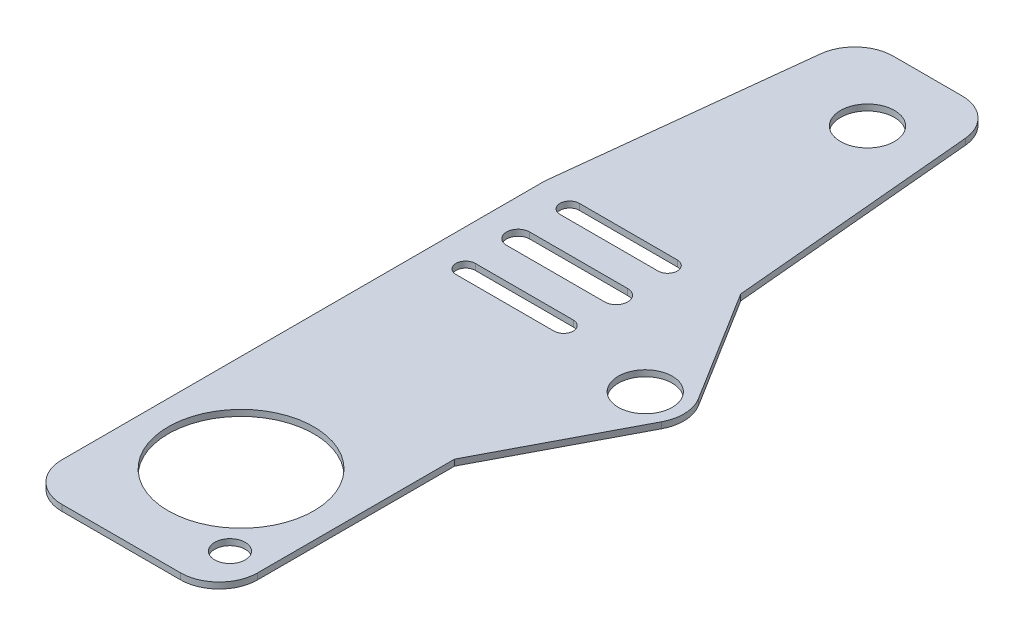
SolidWorks part; units mm, degrees
ref_plane "Front" through (0, 0, 0) normal (0, 0, 1) x (1, 0, 0)
ref_plane "Top" through (0, 0, 0) normal (0, 1, 0) x (1, 0, 0)
ref_plane "Right" through (0, 0, 0) normal (1, 0, 0) x (0, 0, -1)
sketch "Sketch1" plane through (0, 0, 0) normal (0, 1, 0) x (1, 0, 0)
  line L0 (10.4543, 228.6) -> (0, 135.3627)
  line L1 (0, 0) -> (50.8, 0)
  line L2 (0, 0) -> (0, 228.6)
  line L3 (0, 228.6) -> (50.8, 228.6)
  line L4 (50.8, 0) -> (50.8, 228.6)
  line L5 (42.3273, 228.6) -> (50.8, 135.3627)
  line L8 (50.8, 0) -> (24.327, 0)
  line L9 (50.8, 0) -> (50.8, -15)
  line L10 (50.8, -15) -> (24.327, -15)
  line L11 (24.327, 0) -> (24.327, -15)
  line L16 (50.8, 120.6192) -> (50.8, 104.4882)
  line L18 (50.8, 64.8791) -> (50.8, 87.4235)
  circle A2 centre (24.327, 25.5092) radius 5.969
  circle A3 centre (42.3273, 11.2956) radius 3.9601
  circle A12 centre (60.4, 101.001) radius 10
  circle A13 centre (29.5042, 189.5572) radius 7
  circle A14 centre (25.2716, 31.2259) radius 18.9
  circle A15 centre (24.1018, 118.7849) radius 2.875
  dimension "D3" = 20
  dimension "D4" = 11.938
  dimension "D5" = 15
  dimension "D6" = 14
  dimension "D1" = 50.8
  dimension "D2" = 228.6
extrude "Boss-Extrude1" add sketch "Sketch1" along normal blind 1.5875 contours L1 L4 L3 L0 L2 region at (25.4467, 0, -115.7065)
sketch "Sketch4" plane through (0, 0, -228.6) normal (0, 0, -1) x (-1, 0, 0)
  line L1 (-61.3109, 11.9192) -> (4.9615, 11.9192)
  line L2 (-61.3109, 11.9192) -> (-61.3109, -15.8811)
  line L3 (-61.3109, -15.8811) -> (4.9615, -15.8811)
  line L4 (4.9615, 11.9192) -> (4.9615, -15.8811)
extrude "Cut-Extrude2" cut sketch "Sketch4" against normal blind 20
fillet "Fillet3" radius 10 1 edges at (44.1447, 0.7937, -208.6)
fillet "Fillet4" radius 10 3 edges at (50.8, 0.7937, 0) (0, 0.7937, 0) (8.2118, 0.7937, -208.6)
sketch "Sketch6" plane through (0, 1.5875, 0) normal (0, 1, 0) x (1, 0, 0)
  line L0 (68.8909, 106.2834) -> (50.8, 135.3627)
  line L1 (50.8, 135.3627) -> (50.8, 103.801)
  line L2 (69.2582, 96.3607) -> (50.8, 61.1242)
  line L3 (50.8, 10) -> (50.8, 98.201) construction
  line L4 (50.8, 61.1242) -> (50.8, 96.3607)
  line L5 (50.8, 96.3607) -> (50.8, 98.201)
  circle A0 centre (60.4, 101.001) radius 10
  line M4 (50.8, 10) -> (50.8, 98.201)
  arc M5 (50.8, 98.201) -> (50.8, 103.801) centre (60.4, 101.001) cw
  line M6 (50.8, 103.801) -> (50.8, 135.3627)
extrude "Boss-Extrude3" add sketch "Sketch6" against normal blind 1.5875 contours A0 L0 M6 | A0 M5 | A0 L2 M4 region at (55.8248, 1.5875, -118.0301) region at (60.4, 1.5875, -101.001) region at (56.0341, 1.5875, -82.1407)
sketch "Sketch7" plane through (0, 1.5875, 0) normal (0, 1, 0) x (1, 0, 0)
  circle A0 centre (60.4, 101.001) radius 7
  dimension "D1" = 14
extrude "Cut-Extrude3" cut sketch "Sketch7" against normal blind 1.5875
sketch "Sketch8" plane through (0, 1.5875, 0) normal (0, 1, 0) x (1, 0, 0)
  line L1 (9.492, 121.9099) -> (34.9257, 121.9099)
  line L2 (9.492, 121.9099) -> (9.492, 115.9099)
  line L3 (9.492, 115.9099) -> (34.9257, 115.9099)
  line L4 (34.9257, 121.9099) -> (34.9257, 115.9099)
  line L5 (9.492, 134.7849) -> (34.9257, 134.7849)
  line L6 (9.492, 134.7849) -> (9.492, 129.7849)
  line L7 (9.492, 129.7849) -> (34.9257, 129.7849)
  line L8 (34.9257, 134.7849) -> (34.9257, 129.7849)
  line L9 (9.492, 107.7849) -> (34.9257, 107.7849)
  line L10 (9.492, 107.7849) -> (9.492, 102.7849)
  line L11 (9.492, 102.7849) -> (34.9257, 102.7849)
  line L12 (34.9257, 107.7849) -> (34.9257, 102.7849)
  circle A0 centre (9.492, 118.9099) radius 3
  circle A1 centre (34.9257, 118.9099) radius 3
  circle A2 centre (23.3804, 132.2849) radius 2.5
  circle A4 centre (24.1018, 118.7849) radius 2.875 construction
  circle A5 centre (9.492, 132.2849) radius 2.5
  circle A6 centre (34.9257, 132.2849) radius 2.5
  circle A7 centre (24.29, 105.2849) radius 2.5
  circle A8 centre (24.1018, 118.7849) radius 2.875 construction
  circle A9 centre (9.492, 105.2849) radius 2.5
  circle A10 centre (34.9257, 105.2849) radius 2.5
  circle M15 centre (24.1018, 118.7849) radius 2.875
  dimension "D1" = 13.5
  dimension "D2" = 13.5
extrude "Cut-Extrude4" cut sketch "Sketch8" against normal blind 10 contours A1 L1 A0 L3 M15 | L2 A0 | L2 A0 | M15 | L4 A1 | L4 A1 | A5 L7 A2 L5 | A9 L11 A7 L9 | A10 L9 A7 L11 | A7 | A0 | A5 | A2 | A6 | L7 L8 L5 L6 | A10 | A9 region at (10.7653, 1.5875, -118.9099) region at (24.1018, 1.5875, -118.7849) region at (22.2089, 1.5875, -121.6486) region at (8.2188, 1.5875, -118.9099) region at (36.199, 1.5875, -118.9099) region at (33.6525, 1.5875, -118.9099) region at (16.4362, 1.5875, -132.2849) region at (16.891, 1.5875, -105.2849) region at (29.6079, 1.5875, -105.2849) region at (24.29, 1.5875, -105.2849) body kept at (17.1532, 0, -208.6)
equation "\"7i\"=101.6"
